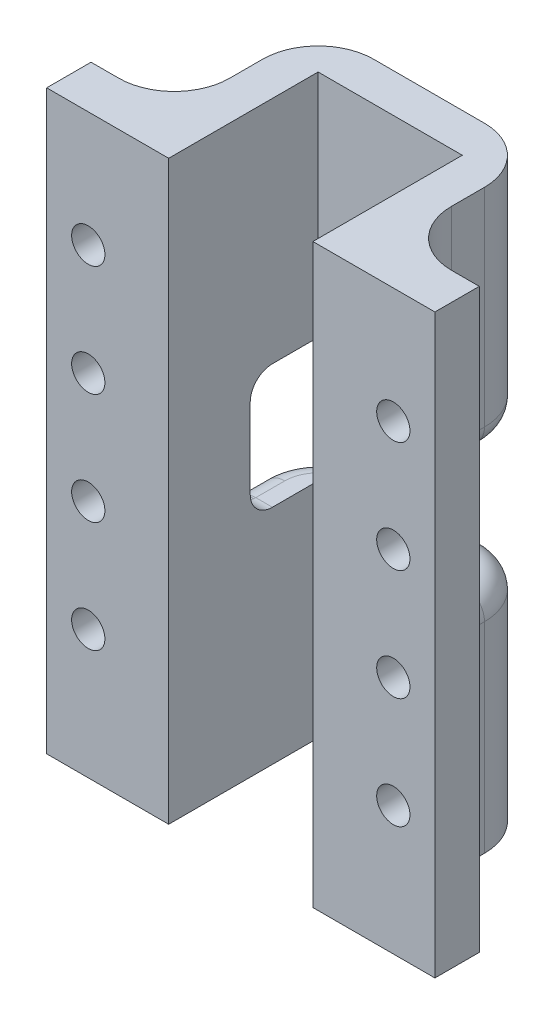
SolidWorks part; units mm, degrees
ref_plane "Спереди" through (0, 0, 0) normal (0, 0, 1) x (1, 0, 0)
ref_plane "Сверху" through (0, 0, 0) normal (0, 1, 0) x (1, 0, 0)
ref_plane "Справа" through (0, 0, 0) normal (1, 0, 0) x (0, 0, -1)
sketch "Эскиз1" plane through (0, 0, 0) normal (0, 1, 0) x (1, 0, 0)
  line L0 (-17.5, -8.4853) -> (-6.5, -8.4853)
  line L2 (-6.5, -8.4853) -> (-6.5, 5.0147)
  line L3 (-6.5, 4.9853) -> (6.5, 4.9853)
  line L4 (6.5, -8.4853) -> (6.5, 4.9853)
  line L5 (6.5, -8.4853) -> (17.5, -8.4853)
  line L6 (17.5, -8.4853) -> (17.5, -4.4853)
  line L7 (17.5, -4.4853) -> (10, -4.4853)
  line L8 (10, -4.4853) -> (10, 8.4853)
  line L9 (10, 8.4853) -> (-10, 8.4853)
  line L10 (-10, 8.4853) -> (-10, -4.4853)
  line L11 (-10, -4.4853) -> (-17.5, -4.4853)
  line L12 (-17.5, -4.4853) -> (-17.5, -8.4853)
  point P2 (17.5, -6.4853)
  dimension "D2" = 4
  dimension "D3" = 12.9706
  dimension "D4" = 3.5
  dimension "D5" = 4
  dimension "D6" = 12.9706
  dimension "D7" = 20
  dimension "D8" = 13
  dimension "D9" = 7.5
  dimension "D10" = 35
  dimension "D11" = 7.5
  dimension "D12" = 3.5
  dimension "D13" = 3.5
extrude "Бобышка-Вытянуть1" add sketch "Эскиз1" along normal blind 52 contours L11 L12 L0 L2 L3 L4 L5 L6 L7 L8 L9 L10 | L3 L4 L5 L6 L7 L8 L9 L10 L11 L12 L0 L2 region at (-17.111, 0, 6.4853)
fillet "Скругление1" radius 5 4 edges at (-10, 26, -8.4853) (10, 26, -8.4853) (-10, 26, 4.4853) (10, 26, 4.4853)
ref_plane "Плоскость1" through (0, 0, 18.4853) normal (0, 0, 1) x (1, 0, 0)
ref_plane "Плоскость2" through (0, 0, 4.4853) normal (0, 0, -1) x (-1, 0, 0)
sketch "Эскиз2" plane through (0, 0, 4.4853) normal (0, 0, -1) x (-1, 0, 0)
  line L0 (13.75, 52) -> (13.75, 0) construction
  line L10 (-13.75, 52) -> (-13.75, 0) construction
  circle A8 centre (13.75, 41.6) radius 1.5
  circle A9 centre (13.75, 31.6) radius 1.5
  circle A10 centre (13.75, 21.6) radius 1.5
  circle A11 centre (13.75, 11.6) radius 1.5
  circle A12 centre (-13.75, 41.6) radius 1.5
  circle A13 centre (-13.75, 31.6) radius 1.5
  circle A14 centre (-13.75, 21.6) radius 1.5
  circle A15 centre (-13.75, 11.6) radius 1.5
  dimension "D4" = 4
  dimension "D3" = 4
extrude "Вырез-Вытянуть1" cut sketch "Эскиз2" against normal blind 10 and the other way blind 10
sketch "Эскиз3" plane through (0, 0, 4.4853) normal (0, 0, -1) x (-1, 0, 0)
  line L0 (0, 52) -> (0, 0) construction
  line L1 (13.75, 38.4246) -> (16.5, 40.0123)
  line L2 (16.5, 40.0123) -> (16.5, 43.1877)
  line L3 (16.5, 43.1877) -> (13.75, 44.7754)
  line L4 (13.75, 44.7754) -> (11, 43.1877)
  line L5 (11, 43.1877) -> (11, 40.0123)
  line L6 (11, 40.0123) -> (13.75, 38.4246)
  line L7 (-5, 52) -> (5, 52) construction
  line L8 (-11, 40.0123) -> (-13.75, 38.4246)
  line L9 (-11, 43.1877) -> (-11, 40.0123)
  line L10 (-13.75, 44.7754) -> (-11, 43.1877)
  line L11 (-16.5, 43.1877) -> (-13.75, 44.7754)
  line L12 (-16.5, 40.0123) -> (-16.5, 43.1877)
  line L13 (-13.75, 38.4246) -> (-16.5, 40.0123)
  line L14 (13.75, 28.4246) -> (16.5, 30.0123)
  line L15 (16.5, 30.0123) -> (16.5, 33.1877)
  line L16 (16.5, 33.1877) -> (13.75, 34.7754)
  line L17 (13.75, 34.7754) -> (11, 33.1877)
  line L18 (11, 33.1877) -> (11, 30.0123)
  line L19 (11, 30.0123) -> (13.75, 28.4246)
  line L20 (-11, 30.0123) -> (-13.75, 28.4246)
  line L21 (-13.75, 28.4246) -> (-16.5, 30.0123)
  line L22 (-16.5, 30.0123) -> (-16.5, 33.1877)
  line L23 (-16.5, 33.1877) -> (-13.75, 34.7754)
  line L24 (-13.75, 34.7754) -> (-11, 33.1877)
  line L25 (-11, 33.1877) -> (-11, 30.0123)
  line L26 (13.75, 18.4246) -> (16.5, 20.0123)
  line L27 (16.5, 20.0123) -> (16.5, 23.1877)
  line L28 (16.5, 23.1877) -> (13.75, 24.7754)
  line L29 (13.75, 24.7754) -> (11, 23.1877)
  line L30 (11, 23.1877) -> (11, 20.0123)
  line L31 (11, 20.0123) -> (13.75, 18.4246)
  line L32 (-11, 20.0123) -> (-13.75, 18.4246)
  line L33 (-13.75, 18.4246) -> (-16.5, 20.0123)
  line L34 (-16.5, 20.0123) -> (-16.5, 23.1877)
  line L35 (-16.5, 23.1877) -> (-13.75, 24.7754)
  line L36 (-13.75, 24.7754) -> (-11, 23.1877)
  line L37 (-11, 23.1877) -> (-11, 20.0123)
  line L38 (13.75, 8.4246) -> (16.5, 10.0123)
  line L39 (16.5, 10.0123) -> (16.5, 13.1877)
  line L40 (16.5, 13.1877) -> (13.75, 14.7754)
  line L41 (13.75, 14.7754) -> (11, 13.1877)
  line L42 (11, 13.1877) -> (11, 10.0123)
  line L43 (11, 10.0123) -> (13.75, 8.4246)
  line L44 (-11, 10.0123) -> (-13.75, 8.4246)
  line L45 (-13.75, 8.4246) -> (-16.5, 10.0123)
  line L46 (-16.5, 10.0123) -> (-16.5, 13.1877)
  line L47 (-16.5, 13.1877) -> (-13.75, 14.7754)
  line L48 (-13.75, 14.7754) -> (-11, 13.1877)
  line L49 (-11, 13.1877) -> (-11, 10.0123)
  circle A0 centre (13.75, 41.6) radius 2.75 construction
  dimension "D1" = 5.5
extrude "Вырез-Вытянуть2" cut sketch "Эскиз3" against normal blind 1.5 and the other way blind 10
sketch "Эскиз4" plane through (-17.5, 0, 0) normal (-1, 0, 0) x (0, 0, 1)
  line L1 (1.1361, 20.0799) -> (-11.9234, 20.0799)
  line L3 (1.1361, 31.2802) -> (-11.9234, 31.2802)
  line L4 (-11.9234, 20.0799) -> (-11.9234, 31.2802)
  line L5 (1.1361, 20.0799) -> (1.1361, 31.2802)
extrude "Вырез-Вытянуть3" cut sketch "Эскиз4" against normal blind 34
fillet "Скругление2" radius 2 4 edges at (8.3902, 31.2802, 1.1361) (8.3902, 20.0799, 1.1361) (-8.3902, 31.2802, 1.1361) (-8.3902, 20.0799, 1.1361)
fillet "Скругление3" radius 2 20 edges at (-8.5355, 20.0799, -7.0208) (-10, 20.0799, -2.1746) (-10, 20.0876, -0.6886) (-10.1566, 20.8677, 0.7269) (-10.2804, 25.68, 1.1361) (-10.1273, 30.6362, 0.6062) (-10, 31.2725, -0.6886) (-10, 31.2802, -2.1746) (-8.5355, 31.2802, -7.0208) (0, 31.2802, -8.4853) (8.5355, 31.2802, -7.0208) (10, 31.2802, -2.1746) (10, 31.2725, -0.6886) (10.1566, 30.4923, 0.7269) (10.2804, 25.68, 1.1361) (10.1273, 20.7238, 0.6062) (10, 20.0876, -0.6886) (10, 20.0799, -2.1746) (8.5355, 20.0799, -7.0208) (0, 20.0799, -8.4853)
